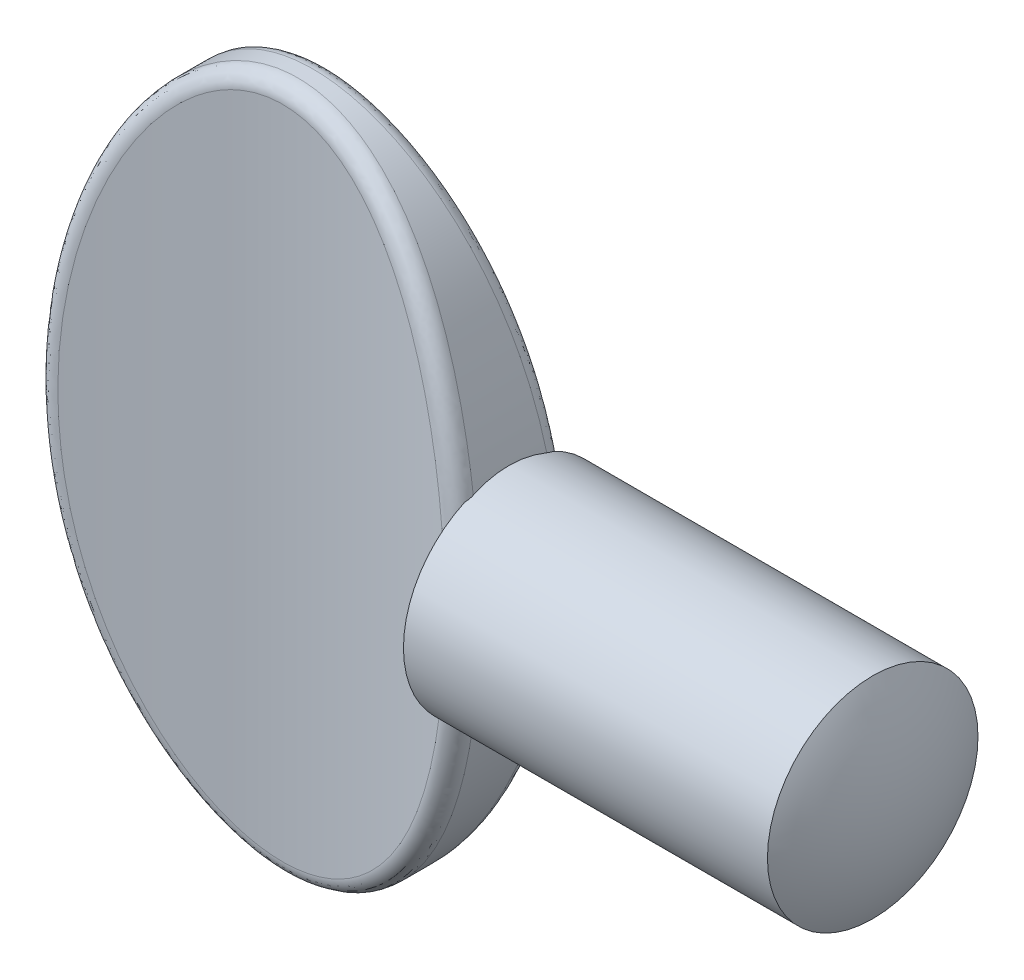
SolidWorks part; units mm, degrees
ref_plane "Front" through (0, 0, 0) normal (0, 0, 1) x (1, 0, 0)
ref_plane "Top" through (0, 0, 0) normal (0, 1, 0) x (1, 0, 0)
ref_plane "Right" through (0, 0, 0) normal (1, 0, 0) x (0, 0, -1)
ref_axis "Axis1" through (-50, 0, 0) along (1, 0, 0)
sketch "Sketch1" plane through (0, 0, 0) normal (0, 0, 1) x (1, 0, 0)
  line L0 (0, 0) -> (9.906, 0) construction
  line L1 (4.7413, -1.7526) -> (4.7413, 1.7526)
  line L2 (4.7413, -1.7526) -> (3.3847, -1.7526) construction
  ellipse E0 centre (0, 0) end of major axis (0, -5.715) minor radius 3.556
  dimension "D2" = 1.1853
  dimension "B" = 7.112
  dimension "L" = 6.35
extrude "Extrude1" add sketch "Sketch1" along normal mid plane 2.032
sketch "Sketch2" plane through (0, 0, 0) normal (0, 1, 0) x (1, 0, 0)
  line L0 (3.556, 1.016) -> (-3.556, 1.016) construction
  line L1 (0, 0) -> (0, 1.1721) construction
  line L2 (-1.7991, 0) -> (2.0444, 0) construction
  line L3 (-3.556, -1.016) -> (3.556, -1.016) construction
  line L6 (-3.556, 1.016) -> (-3.556, -1.016)
  line L7 (3.556, 1.016) -> (3.556, -1.016)
  arc A0 (-3.556, 1.016) -> (3.556, 1.016) centre (0, 10.6553) ccw
  arc A1 (-3.556, -1.016) -> (3.556, -1.016) centre (0, -10.6553) cw
extrude "Cut-Extrude1" cut sketch "Sketch2" against normal through all and the other way through all flip side to cut
fillet "Fillet3" radius 0.254 2 edges at (-3.4679, -1.2641, 0.984) (0.2073, 5.7053, -0.3831)
sketch "Sketch3" plane through (0, 0, 0) normal (0, 1, 0) x (1, 0, 0)
  line L0 (9.906, 0) -> (9.906, -2.4775) construction
  line L1 (0, 0) -> (21.0288, 0) construction
  line L2 (0, 0) -> (9.906, 0) construction
  line L3 (4.7413, 1.7526) -> (4.7413, 0) construction
  line L4 (4.7413, 1.7526) -> (9.4441, 1.7526)
  line L6 (4.7413, 1.7526) -> (3.3847, 1.7526)
  line L7 (2.5775, 0.7096) -> (2.5775, 0)
  line L8 (3.3847, 0) -> (3.3847, 1.7526) construction
  line L9 (2.5775, 0) -> (9.906, 0)
  arc A0 (3.3847, 1.7526) -> (2.5775, 0.7096) centre (2.3072, 1.7526) cw
  arc A1 (9.906, 0) -> (9.4441, 1.7526) centre (6.35, 0) ccw
  arc A3 (-3.556, 1.016) -> (3.556, 1.016) centre (0, 10.6553) ccw construction
revolve "Revolve1" add sketch "Sketch3" angle 360 about L0
cosmetic thread "Cosmetic Thread1" [suppressed]
sketch "Sketch4" plane through (0, 0, 0) normal (0, 0, 1) x (1, 0, 0)
  line L0 (0, 0) -> (27.7993, 0) construction
  line L1 (9.2388, 1.7526) -> (9.4441, 1.397)
  line L2 (9.4441, 1.397) -> (9.6494, 1.7526)
  line L3 (9.6494, 1.7526) -> (9.6494, 2.1632)
  line L4 (9.6494, 2.1632) -> (9.2388, 2.1632)
  line L5 (9.2388, 2.1632) -> (9.2388, 1.7526)
  line L6 (9.4441, 1.7526) -> (9.4441, -1.7526) construction
  dimension "D1" = 2.794
  dimension "D2" = 3.5052
revolve "Cut-Revolve10" [suppressed] cut sketch "Sketch4" angle 360 about L0
pattern_linear "LPattern10" [suppressed] count 12 along (-1, 0, 0) of bodies 109
equation "\"D2@Sketch1\" = \"B@Sketch1\" / 6"
equation "\"D1@Fillet3\" = \"C1@Sketch2\" / 3"
equation "\"DIA@Sketch3\" = \"D@Sketch1\""
equation "\"D1@Sketch4\" = \"D2@Cosmetic Thread1\""
equation "\"D2@Sketch4\" = \"DIA@Sketch3\""
equation "\"D1@LPattern10\" = \"L@Sketch1\" / \"P@LPattern10\"  - 1"
